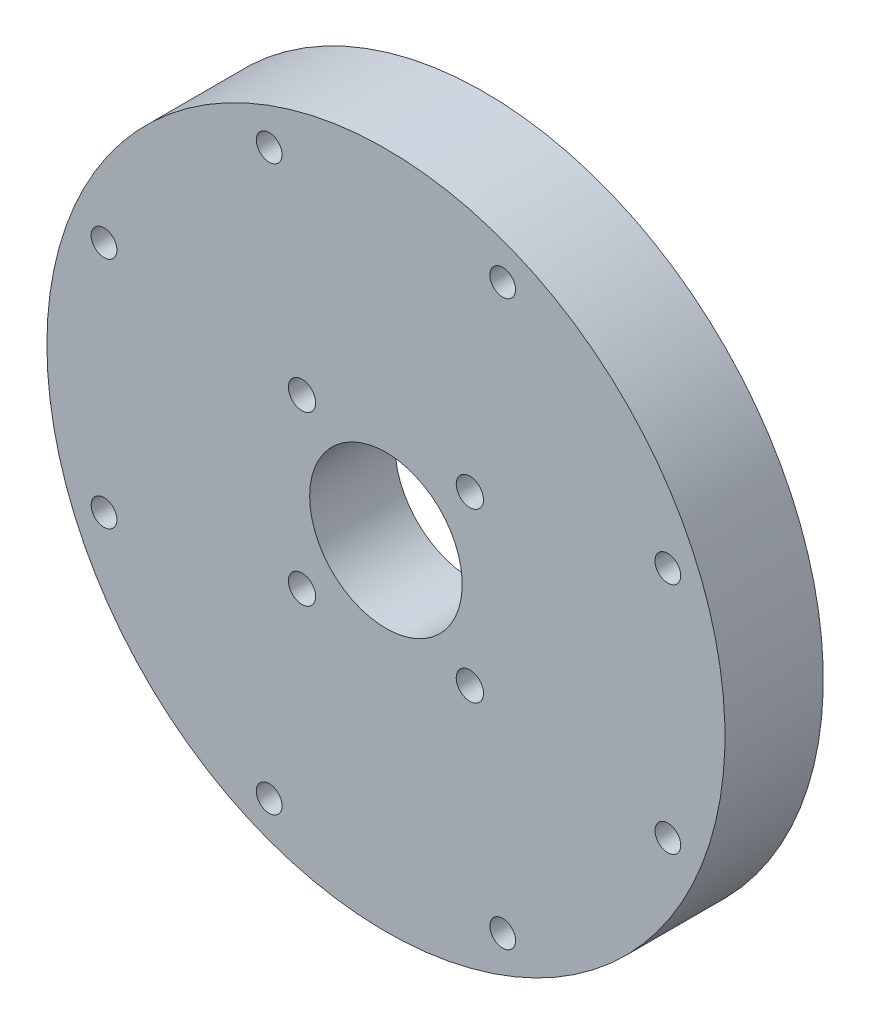
SolidWorks part; units mm, degrees
material "6061-T6 (SS)"
ref_plane "Front Plane" through (0, 0, 0) normal (0, 0, 1) x (1, 0, 0)
ref_plane "Top Plane" through (0, 0, 0) normal (0, 1, 0) x (1, 0, 0)
ref_plane "Right Plane" through (0, 0, 0) normal (1, 0, 0) x (0, 0, -1)
curve "Volute Curve"
  spline degree 3 poles (34.2618, 0, 0) (34.2648, 0.0718, 0) (34.2707, 0.2156, 0) (34.2778, 0.4312, 0) (34.2837, 0.647, 0) (34.2882, 0.8628, 0) (34.2914, 1.0787, 0) (34.2932, 1.2947, 0) (34.2937, 1.5108, 0) (34.2929, 1.7269, 0) (34.2907, 1.9431, 0) (34.2871, 2.1593, 0) (34.2822, 2.3756, 0) (34.2759, 2.5919, 0) (34.2683, 2.8082, 0) (34.2593, 3.0245, 0) (34.2489, 3.2407, 0) (34.2372, 3.457, 0) (34.2242, 3.6733, 0) (34.2098, 3.8895, 0) (34.194, 4.1058, 0) (34.1768, 4.3219, 0) (34.1583, 4.538, 0) (34.1385, 4.7541, 0) (34.1173, 4.9701, 0) (34.0947, 5.186, 0) (34.0708, 5.4018, 0) (34.0454, 5.6175, 0) (34.0188, 5.8331, 0) (33.9908, 6.0486, 0) (33.9614, 6.264, 0) (33.9306, 6.4793, 0) (33.8985, 6.6944, 0) (33.8651, 6.9094, 0) (33.8303, 7.1242, 0) (33.7941, 7.3388, 0) (33.7566, 7.5533, 0) (33.7177, 7.7676, 0) (33.6774, 7.9817, 0) (33.6358, 8.1956, 0) (33.5929, 8.4093, 0) (33.5486, 8.6228, 0) (33.5029, 8.8361, 0) (33.4559, 9.0491, 0) (33.4076, 9.2619, 0) (33.3579, 9.4745, 0) (33.3068, 9.6868, 0) (33.2544, 9.8988, 0) (33.2006, 10.1105, 0) (33.1456, 10.322, 0) (33.0891, 10.5332, 0) (33.0313, 10.744, 0) (32.9722, 10.9546, 0) (32.9118, 11.1648, 0) (32.85, 11.3748, 0) (32.7869, 11.5843, 0) (32.7224, 11.7936, 0) (32.6566, 12.0025, 0) (32.5895, 12.211, 0) (32.521, 12.4192, 0) (32.4513, 12.627, 0) (32.3802, 12.8344, 0) (32.3077, 13.0414, 0) (32.234, 13.248, 0) (32.1589, 13.4542, 0) (32.0826, 13.6599, 0) (32.0049, 13.8653, 0) (31.9259, 14.0702, 0) (31.8456, 14.2747, 0) (31.764, 14.4787, 0) (31.6811, 14.6823, 0) (31.5968, 14.8854, 0) (31.5113, 15.088, 0) (31.4245, 15.2901, 0) (31.3364, 15.4917, 0) (31.247, 15.6929, 0) (31.1563, 15.8935, 0) (31.0644, 16.0936, 0) (30.9711, 16.2932, 0) (30.8766, 16.4922, 0) (30.7808, 16.6907, 0) (30.6837, 16.8886, 0) (30.5854, 17.086, 0) (30.4858, 17.2829, 0) (30.3849, 17.4791, 0) (30.2828, 17.6748, 0) (30.1794, 17.8698, 0) (30.0747, 18.0643, 0) (29.9688, 18.2582, 0) (29.8617, 18.4514, 0) (29.7533, 18.644, 0) (29.6437, 18.836, 0) (29.5328, 19.0274, 0) (29.4208, 19.2181, 0) (29.3074, 19.4081, 0) (29.1929, 19.5975, 0) (29.0771, 19.7862, 0) (28.9601, 19.9742, 0) (28.842, 20.1616, 0) (28.7226, 20.3482, 0) (28.602, 20.5342, 0) (28.4801, 20.7194, 0) (28.3571, 20.904, 0) (28.233, 21.0877, 0) (28.1076, 21.2708, 0) (27.981, 21.4531, 0) (27.8533, 21.6347, 0) (27.7243, 21.8155, 0) (27.5942, 21.9956, 0) (27.463, 22.1748, 0) (27.3306, 22.3533, 0) (27.197, 22.531, 0) (27.0623, 22.708, 0) (26.9264, 22.8841, 0) (26.7894, 23.0594, 0) (26.6512, 23.2339, 0) (26.5119, 23.4075, 0) (26.3715, 23.5804, 0) (26.23, 23.7524, 0) (26.0873, 23.9235, 0) (25.9435, 24.0938, 0) (25.7987, 24.2632, 0) (25.6527, 24.4318, 0) (25.5056, 24.5995, 0) (25.3574, 24.7663, 0) (25.2082, 24.9322, 0) (25.0578, 25.0973, 0) (24.9064, 25.2614, 0) (24.7539, 25.4246, 0) (24.6003, 25.5869, 0) (24.4457, 25.7483, 0) (24.29, 25.9087, 0) (24.1333, 26.0682, 0) (23.9755, 26.2268, 0) (23.8167, 26.3844, 0) (23.6569, 26.541, 0) (23.496, 26.6967, 0) (23.3341, 26.8514, 0) (23.1712, 27.0051, 0) (23.0073, 27.1579, 0) (22.8424, 27.3096, 0) (22.6765, 27.4604, 0) (22.5096, 27.6101, 0) (22.3417, 27.7589, 0) (22.1728, 27.9066, 0) (22.003, 28.0533, 0) (21.8322, 28.199, 0) (21.6604, 28.3436, 0) (21.4877, 28.4872, 0) (21.314, 28.6297, 0) (21.1394, 28.7712, 0) (20.9639, 28.9116, 0) (20.7874, 29.051, 0) (20.61, 29.1892, 0) (20.4317, 29.3264, 0) (20.2524, 29.4626, 0) (20.0723, 29.5976, 0) (19.8913, 29.7315, 0) (19.7094, 29.8643, 0) (19.5266, 29.996, 0) (19.3429, 30.1266, 0) (19.1584, 30.2561, 0) (18.973, 30.3844, 0) (18.7867, 30.5116, 0) (18.5996, 30.6377, 0) (18.4117, 30.7626, 0) (18.2229, 30.8864, 0) (18.0333, 31.009, 0) (17.8429, 31.1304, 0) (17.6516, 31.2507, 0) (17.4596, 31.3698, 0) (17.2667, 31.4878, 0) (17.0731, 31.6045, 0) (16.8786, 31.7201, 0) (16.6834, 31.8344, 0) (16.4875, 31.9476, 0) (16.2907, 32.0596, 0) (16.0932, 32.1703, 0) (15.895, 32.2799, 0) (15.696, 32.3882, 0) (15.4963, 32.4953, 0) (15.2959, 32.6012, 0) (15.0947, 32.7058, 0) (14.8929, 32.8092, 0) (14.6903, 32.9114, 0) (14.487, 33.0123, 0) (14.2831, 33.1119, 0) (14.0784, 33.2103, 0) (13.8731, 33.3075, 0) (13.6672, 33.4033, 0) (13.4606, 33.4979, 0) (13.2533, 33.5912, 0) (13.0454, 33.6833, 0) (12.8368, 33.774, 0) (12.6277, 33.8635, 0) (12.4179, 33.9517, 0) (12.2075, 34.0385, 0) (11.9965, 34.1241, 0) (11.7849, 34.2084, 0) (11.5727, 34.2913, 0) (11.36, 34.373, 0) (11.1467, 34.4533, 0) (10.9328, 34.5323, 0) (10.7183, 34.61, 0) (10.5034, 34.6863, 0) (10.2879, 34.7613, 0) (10.0718, 34.835, 0) (9.8553, 34.9074, 0) (9.6382, 34.9783, 0) (9.4206, 35.048, 0) (9.2025, 35.1163, 0) (8.984, 35.1832, 0) (8.765, 35.2488, 0) (8.5455, 35.313, 0) (8.3255, 35.3759, 0) (8.1051, 35.4374, 0) (7.8842, 35.4975, 0) (7.6629, 35.5562, 0) (7.4412, 35.6136, 0) (7.2191, 35.6696, 0) (6.9965, 35.7242, 0) (6.7736, 35.7774, 0) (6.5503, 35.8292, 0) (6.3265, 35.8796, 0) (6.1024, 35.9287, 0) (5.878, 35.9763, 0) (5.6532, 36.0225, 0) (5.428, 36.0674, 0) (5.2025, 36.1108, 0) (4.9766, 36.1528, 0) (4.7505, 36.1934, 0) (4.524, 36.2326, 0) (4.2972, 36.2704, 0) (4.0701, 36.3067, 0) (3.8428, 36.3417, 0) (3.6151, 36.3752, 0) (3.3872, 36.4073, 0) (3.159, 36.438, 0) (2.9306, 36.4672, 0) (2.7019, 36.495, 0) (2.473, 36.5214, 0) (2.2439, 36.5463, 0) (2.0146, 36.5699, 0) (1.785, 36.5919, 0) (1.5553, 36.6126, 0) (1.3253, 36.6318, 0) (1.0952, 36.6495, 0) (0.8649, 36.6658, 0) (0.6345, 36.6807, 0) (0.4039, 36.6941, 0) (0.1731, 36.706, 0) (-0.0577, 36.7166, 0) (-0.2887, 36.7256, 0) (-0.5199, 36.7332, 0) (-0.7511, 36.7394, 0) (-0.9824, 36.7441, 0) (-1.2138, 36.7474, 0) (-1.4453, 36.7492, 0) (-1.6769, 36.7495, 0) (-1.9085, 36.7484, 0) (-2.1402, 36.7458, 0) (-2.3719, 36.7418, 0) (-2.6037, 36.7363, 0) (-2.8355, 36.7293, 0) (-3.0673, 36.7209, 0) (-3.2991, 36.711, 0) (-3.5309, 36.6997, 0) (-3.7627, 36.6869, 0) (-3.9944, 36.6726, 0) (-4.2262, 36.6569, 0) (-4.4579, 36.6397, 0) (-4.6895, 36.6211, 0) (-4.9211, 36.6009, 0) (-5.1526, 36.5794, 0) (-5.3841, 36.5563, 0) (-5.6154, 36.5318, 0) (-5.8467, 36.5059, 0) (-6.0779, 36.4784, 0) (-6.3089, 36.4495, 0) (-6.5399, 36.4192, 0) (-6.7706, 36.3874, 0) (-7.0013, 36.3541, 0) (-7.2318, 36.3194, 0) (-7.4621, 36.2832, 0) (-7.6923, 36.2455, 0) (-7.9223, 36.2064, 0) (-8.1521, 36.1658, 0) (-8.3817, 36.1238, 0) (-8.6111, 36.0803, 0) (-8.8403, 36.0354, 0) (-9.0693, 35.989, 0) (-9.298, 35.9411, 0) (-9.5265, 35.8918, 0) (-9.7548, 35.8411, 0) (-9.9827, 35.7889, 0) (-10.2105, 35.7352, 0) (-10.4379, 35.6802, 0) (-10.665, 35.6236, 0) (-10.8919, 35.5656, 0) (-11.1184, 35.5062, 0) (-11.3446, 35.4453, 0) (-11.5705, 35.383, 0) (-11.7961, 35.3193, 0) (-12.0213, 35.2541, 0) (-12.2461, 35.1875, 0) (-12.4706, 35.1194, 0) (-12.6948, 35.0499, 0) (-12.9185, 34.979, 0) (-13.1419, 34.9067, 0) (-13.3648, 34.8329, 0) (-13.5874, 34.7578, 0) (-13.8095, 34.6812, 0) (-14.0312, 34.6031, 0) (-14.2525, 34.5237, 0) (-14.4734, 34.4429, 0) (-14.6937, 34.3606, 0) (-14.9137, 34.2769, 0) (-15.1331, 34.1918, 0) (-15.3521, 34.1054, 0) (-15.5706, 34.0175, 0) (-15.7885, 33.9282, 0) (-16.006, 33.8375, 0) (-16.223, 33.7455, 0) (-16.4394, 33.652, 0) (-16.6553, 33.5572, 0) (-16.8707, 33.461, 0) (-17.0855, 33.3634, 0) (-17.2997, 33.2644, 0) (-17.5134, 33.164, 0) (-17.7265, 33.0623, 0) (-17.939, 32.9592, 0) (-18.151, 32.8548, 0) (-18.3623, 32.7489, 0) (-18.573, 32.6418, 0) (-18.7831, 32.5332, 0) (-18.9925, 32.4234, 0) (-19.2014, 32.3121, 0) (-19.4095, 32.1996, 0) (-19.6171, 32.0857, 0) (-19.8239, 31.9704, 0) (-20.0301, 31.8538, 0) (-20.2356, 31.7359, 0) (-20.4404, 31.6167, 0) (-20.6445, 31.4962, 0) (-20.8479, 31.3743, 0) (-21.0506, 31.2511, 0) (-21.2526, 31.1267, 0) (-21.4538, 31.0009, 0) (-21.6543, 30.8738, 0) (-21.854, 30.7454, 0) (-22.053, 30.6158, 0) (-22.2512, 30.4848, 0) (-22.4487, 30.3526, 0) (-22.6453, 30.2191, 0) (-22.8412, 30.0843, 0) (-23.0363, 29.9482, 0) (-23.2305, 29.8109, 0) (-23.424, 29.6723, 0) (-23.6166, 29.5325, 0) (-23.8084, 29.3915, 0) (-23.9994, 29.2491, 0) (-24.1895, 29.1056, 0) (-24.3787, 28.9608, 0) (-24.5671, 28.8148, 0) (-24.7546, 28.6676, 0) (-24.9413, 28.5191, 0) (-25.127, 28.3694, 0) (-25.3119, 28.2186, 0) (-25.4958, 28.0665, 0) (-25.6789, 27.9132, 0) (-25.861, 27.7587, 0) (-26.0422, 27.6031, 0) (-26.2224, 27.4463, 0) (-26.4018, 27.2882, 0) (-26.5801, 27.1291, 0) (-26.7576, 26.9687, 0) (-26.934, 26.8072, 0) (-27.1095, 26.6446, 0) (-27.284, 26.4808, 0) (-27.4575, 26.3159, 0) (-27.63, 26.1498, 0) (-27.8015, 25.9826, 0) (-27.972, 25.8143, 0) (-28.1415, 25.6448, 0) (-28.31, 25.4743, 0) (-28.4774, 25.3027, 0) (-28.6438, 25.1299, 0) (-28.8092, 24.9561, 0) (-28.9735, 24.7811, 0) (-29.1367, 24.6051, 0) (-29.2989, 24.4281, 0) (-29.46, 24.2499, 0) (-29.62, 24.0707, 0) (-29.7789, 23.8905, 0) (-29.9368, 23.7092, 0) (-30.0935, 23.5268, 0) (-30.2491, 23.3435, 0) (-30.4036, 23.1591, 0) (-30.557, 22.9737, 0) (-30.7093, 22.7872, 0) (-30.8604, 22.5998, 0) (-31.0104, 22.4114, 0) (-31.1592, 22.2219, 0) (-31.3069, 22.0315, 0) (-31.4534, 21.8402, 0) (-31.5988, 21.6478, 0) (-31.7429, 21.4545, 0) (-31.8859, 21.2602, 0) (-32.0277, 21.065, 0) (-32.1684, 20.8688, 0) (-32.3078, 20.6717, 0) (-32.446, 20.4737, 0) (-32.583, 20.2747, 0) (-32.7188, 20.0748, 0) (-32.8533, 19.8741, 0) (-32.9866, 19.6724, 0) (-33.1187, 19.4698, 0) (-33.2496, 19.2664, 0) (-33.3792, 19.0621, 0) (-33.5075, 18.8569, 0) (-33.6346, 18.6509, 0) (-33.7604, 18.444, 0) (-33.885, 18.2362, 0) (-34.0082, 18.0276, 0) (-34.1302, 17.8182, 0) (-34.2509, 17.608, 0) (-34.3703, 17.397, 0) (-34.4884, 17.1851, 0) (-34.6052, 16.9725, 0) (-34.7207, 16.7591, 0) (-34.8349, 16.5449, 0) (-34.9478, 16.3299, 0) (-35.0593, 16.1141, 0) (-35.1695, 15.8976, 0) (-35.2784, 15.6804, 0) (-35.3859, 15.4624, 0) (-35.4921, 15.2436, 0) (-35.597, 15.0242, 0) (-35.7004, 14.804, 0) (-35.8026, 14.5832, 0) (-35.9033, 14.3616, 0) (-36.0027, 14.1393, 0) (-36.1007, 13.9164, 0) (-36.1973, 13.6928, 0) (-36.2926, 13.4685, 0) (-36.3864, 13.2436, 0) (-36.4789, 13.018, 0) (-36.57, 12.7918, 0) (-36.6596, 12.5649, 0) (-36.7479, 12.3374, 0) (-36.8348, 12.1094, 0) (-36.9202, 11.8807, 0) (-37.0042, 11.6514, 0) (-37.0868, 11.4215, 0) (-37.168, 11.1911, 0) (-37.2477, 10.96, 0) (-37.326, 10.7285, 0) (-37.4029, 10.4963, 0) (-37.4783, 10.2637, 0) (-37.5523, 10.0305, 0) (-37.6248, 9.7967, 0) (-37.6959, 9.5625, 0) (-37.7655, 9.3277, 0) (-37.8337, 9.0925, 0) (-37.9004, 8.8568, 0) (-37.9656, 8.6205, 0) (-38.0293, 8.3839, 0) (-38.0916, 8.1467, 0) (-38.1524, 7.9091, 0) (-38.2117, 7.6711, 0) (-38.2696, 7.4326, 0) (-38.3259, 7.1937, 0) (-38.3808, 6.9544, 0) (-38.4342, 6.7147, 0) (-38.486, 6.4746, 0) (-38.5364, 6.2341, 0) (-38.5853, 5.9932, 0) (-38.6326, 5.7519, 0) (-38.6785, 5.5103, 0) (-38.7229, 5.2684, 0) (-38.7657, 5.0261, 0) (-38.807, 4.7835, 0) (-38.8468, 4.5405, 0) (-38.8851, 4.2973, 0) (-38.9219, 4.0537, 0) (-38.9571, 3.8099, 0) (-38.9908, 3.5657, 0) (-39.023, 3.3213, 0) (-39.0537, 3.0767, 0) (-39.0828, 2.8317, 0) (-39.1104, 2.5866, 0) (-39.1364, 2.3412, 0) (-39.1609, 2.0955, 0) (-39.1839, 1.8497, 0) (-39.2053, 1.6037, 0) (-39.2252, 1.3574, 0) (-39.2435, 1.111, 0) (-39.2603, 0.8644, 0) (-39.2756, 0.6176, 0) (-39.2893, 0.3707, 0) (-39.3014, 0.1236, 0) (-39.312, -0.1236, 0) (-39.321, -0.371, 0) (-39.3285, -0.6185, 0) (-39.3344, -0.866, 0) (-39.3388, -1.1137, 0) (-39.3416, -1.3615, 0) (-39.3428, -1.6093, 0) (-39.3425, -1.8572, 0) (-39.3406, -2.1052, 0) (-39.3372, -2.3532, 0) (-39.3322, -2.6013, 0) (-39.3257, -2.8494, 0) (-39.3175, -3.0975, 0) (-39.3078, -3.3456, 0) (-39.2966, -3.5937, 0) (-39.2838, -3.8418, 0) (-39.2694, -4.0899, 0) (-39.2534, -4.338, 0) (-39.2359, -4.586, 0) (-39.2168, -4.834, 0) (-39.1962, -5.0819, 0) (-39.174, -5.3298, 0) (-39.1502, -5.5776, 0) (-39.1248, -5.8252, 0) (-39.0979, -6.0728, 0) (-39.0694, -6.3203, 0) (-39.0394, -6.5677, 0) (-39.0078, -6.8149, 0) (-38.9746, -7.062, 0) (-38.9399, -7.309, 0) (-38.9036, -7.5558, 0) (-38.8657, -7.8024, 0) (-38.8263, -8.0488, 0) (-38.7853, -8.2951, 0) (-38.7427, -8.5411, 0) (-38.6986, -8.787, 0) (-38.653, -9.0326, 0) (-38.6057, -9.2781, 0) (-38.557, -9.5232, 0) (-38.5066, -9.7682, 0) (-38.4547, -10.0128, 0) (-38.4013, -10.2572, 0) (-38.3463, -10.5014, 0) (-38.2897, -10.7452, 0) (-38.2316, -10.9888, 0) (-38.172, -11.232, 0) (-38.1108, -11.475, 0) (-38.048, -11.7176, 0) (-37.9838, -11.9598, 0) (-37.9179, -12.2018, 0) (-37.8506, -12.4433, 0) (-37.7817, -12.6845, 0) (-37.7112, -12.9254, 0) (-37.6393, -13.1658, 0) (-37.5658, -13.4059, 0) (-37.4907, -13.6455, 0) (-37.4142, -13.8848, 0) (-37.3361, -14.1236, 0) (-37.2565, -14.362, 0) (-37.1753, -14.5999, 0) (-37.0927, -14.8374, 0) (-37.0085, -15.0744, 0) (-36.9228, -15.311, 0) (-36.8357, -15.547, 0) (-36.747, -15.7826, 0) (-36.6568, -16.0177, 0) (-36.5651, -16.2523, 0) (-36.4719, -16.4863, 0) (-36.3772, -16.7199, 0) (-36.281, -16.9528, 0) (-36.1833, -17.1853, 0) (-36.0841, -17.4172, 0) (-35.9834, -17.6485, 0) (-35.8813, -17.8792, 0) (-35.7777, -18.1094, 0) (-35.6726, -18.3389, 0) (-35.566, -18.5679, 0) (-35.458, -18.7962, 0) (-35.3485, -19.0239, 0) (-35.2376, -19.251, 0) (-35.1251, -19.4774, 0) (-35.0113, -19.7032, 0) (-34.896, -19.9283, 0) (-34.7792, -20.1528, 0) (-34.661, -20.3765, 0) (-34.5414, -20.5996, 0) (-34.4203, -20.822, 0) (-34.2978, -21.0437, 0) (-34.1738, -21.2646, 0) (-34.0485, -21.4849, 0) (-33.9217, -21.7044, 0) (-33.7935, -21.9231, 0) (-33.6639, -22.1411, 0) (-33.5329, -22.3584, 0) (-33.4005, -22.5748, 0) (-33.2667, -22.7905, 0) (-33.1315, -23.0054, 0) (-32.995, -23.2195, 0) (-32.857, -23.4328, 0) (-32.7177, -23.6453, 0) (-32.577, -23.8569, 0) (-32.4349, -24.0677, 0) (-32.2915, -24.2777, 0) (-32.1467, -24.4868, 0) (-32.0006, -24.6951, 0) (-31.8531, -24.9025, 0) (-31.7042, -25.109, 0) (-31.5541, -25.3146, 0) (-31.4026, -25.5194, 0) (-31.2497, -25.7232, 0) (-31.0956, -25.9261, 0) (-30.9401, -26.1281, 0) (-30.7833, -26.3292, 0) (-30.6253, -26.5293, 0) (-30.4659, -26.7285, 0) (-30.3052, -26.9267, 0) (-30.1433, -27.124, 0) (-29.98, -27.3203, 0) (-29.8155, -27.5156, 0) (-29.6497, -27.7099, 0) (-29.4827, -27.9032, 0) (-29.3144, -28.0956, 0) (-29.1448, -28.2869, 0) (-28.974, -28.4772, 0) (-28.8019, -28.6664, 0) (-28.6287, -28.8546, 0) (-28.4542, -29.0418, 0) (-28.2784, -29.2279, 0) (-28.1015, -29.413, 0) (-27.9233, -29.597, 0) (-27.744, -29.7799, 0) (-27.5634, -29.9618, 0) (-27.3817, -30.1425, 0) (-27.1987, -30.3221, 0) (-27.0146, -30.5007, 0) (-26.8294, -30.6781, 0) (-26.6429, -30.8544, 0) (-26.4554, -31.0296, 0) (-26.2666, -31.2036, 0) (-26.0767, -31.3765, 0) (-25.8857, -31.5482, 0) (-25.6936, -31.7188, 0) (-25.5003, -31.8882, 0) (-25.306, -32.0564, 0) (-25.1105, -32.2234, 0) (-24.9139, -32.3893, 0) (-24.7162, -32.5539, 0) (-24.5175, -32.7174, 0) (-24.3176, -32.8796, 0) (-24.1167, -33.0406, 0) (-23.9147, -33.2004, 0) (-23.7117, -33.359, 0) (-23.5076, -33.5163, 0) (-23.3025, -33.6724, 0) (-23.0964, -33.8272, 0) (-22.8892, -33.9807, 0) (-22.681, -34.133, 0) (-22.4718, -34.2841, 0) (-22.2616, -34.4338, 0) (-22.0504, -34.5822, 0) (-21.8382, -34.7294, 0) (-21.6251, -34.8752, 0) (-21.4109, -35.0198, 0) (-21.1959, -35.163, 0) (-20.9798, -35.3049, 0) (-20.7628, -35.4455, 0) (-20.5449, -35.5848, 0) (-20.326, -35.7227, 0) (-20.1062, -35.8593, 0) (-19.8855, -35.9945, 0) (-19.6639, -36.1284, 0) (-19.4414, -36.2609, 0) (-19.2181, -36.392, 0) (-18.9938, -36.5218, 0) (-18.7686, -36.6502, 0) (-18.5426, -36.7772, 0) (-18.3158, -36.9028, 0) (-18.0881, -37.027, 0) (-17.8595, -37.1498, 0) (-17.6302, -37.2712, 0) (-17.4, -37.3911, 0) (-17.169, -37.5097, 0) (-16.9372, -37.6268, 0) (-16.7046, -37.7425, 0) (-16.4712, -37.8568, 0) (-16.237, -37.9696, 0) (-16.0021, -38.081, 0) (-15.7664, -38.1909, 0) (-15.53, -38.2994, 0) (-15.2928, -38.4064, 0) (-15.0549, -38.5119, 0) (-14.8163, -38.616, 0) (-14.577, -38.7185, 0) (-14.3369, -38.8196, 0) (-14.0962, -38.9192, 0) (-13.8547, -39.0174, 0) (-13.6126, -39.114, 0) (-13.3699, -39.2091, 0) (-13.1265, -39.3027, 0) (-12.8824, -39.3949, 0) (-12.6377, -39.4854, 0) (-12.3923, -39.5745, 0) (-12.1464, -39.6621, 0) (-11.8998, -39.7481, 0) (-11.6526, -39.8326, 0) (-11.4048, -39.9155, 0) (-11.1565, -39.997, 0) (-10.9076, -40.0768, 0) (-10.6581, -40.1552, 0) (-10.408, -40.2319, 0) (-10.1575, -40.3071, 0) (-9.9063, -40.3808, 0) (-9.6547, -40.4529, 0) (-9.4025, -40.5234, 0) (-9.1499, -40.5924, 0) (-8.8967, -40.6598, 0) (-8.6431, -40.7256, 0) (-8.389, -40.7898, 0) (-8.1344, -40.8524, 0) (-7.8793, -40.9135, 0) (-7.6239, -40.9729, 0) (-7.3679, -41.0308, 0) (-7.1116, -41.087, 0) (-6.8548, -41.1417, 0) (-6.5977, -41.1948, 0) (-6.3401, -41.2462, 0) (-6.0821, -41.2961, 0) (-5.8238, -41.3443, 0) (-5.5651, -41.3909, 0) (-5.3061, -41.4359, 0) (-5.0467, -41.4793, 0) (-4.7869, -41.5211, 0) (-4.5269, -41.5612, 0) (-4.2665, -41.5997, 0) (-4.0058, -41.6366, 0) (-3.7449, -41.6718, 0) (-3.4836, -41.7054, 0) (-3.2221, -41.7374, 0) (-2.9603, -41.7677, 0) (-2.6982, -41.7964, 0) (-2.4359, -41.8234, 0) (-2.1734, -41.8488, 0) (-1.9106, -41.8726, 0) (-1.6477, -41.8947, 0) (-1.3845, -41.9151, 0) (-1.1212, -41.9339, 0) (-0.8576, -41.9511, 0) (-0.5939, -41.9666, 0) (-0.33, -41.9804, 0) (-0.066, -41.9926, 0) (0.1981, -42.0031, 0) (0.4624, -42.012, 0) (0.7268, -42.0192, 0) (0.9914, -42.0247, 0) (1.256, -42.0286, 0) (1.5207, -42.0308, 0) (1.7855, -42.0313, 0) (2.0503, -42.0302, 0) (2.3152, -42.0274, 0) (2.5802, -42.0229, 0) (2.8452, -42.0168, 0) (3.1102, -42.0089, 0) (3.3752, -41.9995, 0) (3.6403, -41.9883, 0) (3.9053, -41.9755, 0) (4.1703, -41.961, 0) (4.4353, -41.9448, 0) (4.7002, -41.927, 0) (4.9651, -41.9075, 0) (5.2299, -41.8863, 0) (5.4947, -41.8634, 0) (5.7594, -41.8389, 0) (6.024, -41.8127, 0) (6.2885, -41.7848, 0) (6.5528, -41.7553, 0) (6.8171, -41.7241, 0) (7.0812, -41.6912, 0) (7.3452, -41.6566, 0) (7.609, -41.6204, 0) (7.8727, -41.5825, 0) (8.1362, -41.5429, 0) (8.3995, -41.5017, 0) (8.6626, -41.4588, 0) (8.9254, -41.4142, 0) (9.1881, -41.3679, 0) (9.4506, -41.32, 0) (9.7128, -41.2705, 0) (9.9747, -41.2192, 0) (10.2364, -41.1663, 0) (10.4979, -41.1118, 0) (10.759, -41.0556, 0) (11.0199, -40.9977, 0) (11.2804, -40.9382, 0) (11.5407, -40.877, 0) (11.8006, -40.8141, 0) (12.0602, -40.7496, 0) (12.3194, -40.6835, 0) (12.5783, -40.6157, 0) (12.8368, -40.5463, 0) (13.0949, -40.4752, 0) (13.3527, -40.4025, 0) (13.6101, -40.3281, 0) (13.867, -40.2521, 0) (14.1235, -40.1745, 0) (14.3797, -40.0952, 0) (14.6353, -40.0143, 0) (14.8905, -39.9318, 0) (15.1453, -39.8476, 0) (15.3996, -39.7618, 0) (15.6534, -39.6744, 0) (15.9067, -39.5854, 0) (16.1596, -39.4948, 0) (16.4119, -39.4025, 0) (16.6637, -39.3087, 0) (16.9149, -39.2132, 0) (17.1657, -39.1161, 0) (17.4158, -39.0174, 0) (17.6654, -38.9172, 0) (17.9145, -38.8153, 0) (18.1629, -38.7118, 0) (18.4108, -38.6068, 0) (18.658, -38.5001, 0) (18.9047, -38.3919, 0) (19.1507, -38.2821, 0) (19.3961, -38.1707, 0) (19.6408, -38.0578, 0) (19.8849, -37.9433, 0) (20.1283, -37.8272, 0) (20.3711, -37.7095, 0) (20.6132, -37.5904, 0) (20.8546, -37.4696, 0) (21.0952, -37.3473, 0) (21.3352, -37.2235, 0) (21.5744, -37.0981, 0) (21.8129, -36.9712, 0) (22.0507, -36.8427, 0) (22.2877, -36.7127, 0) (22.524, -36.5812, 0) (22.7594, -36.4482, 0) (22.9941, -36.3137, 0) (23.228, -36.1776, 0) (23.4611, -36.0401, 0) (23.6934, -35.901, 0) (23.9249, -35.7605, 0) (24.1556, -35.6184, 0) (24.3854, -35.4749, 0) (24.6143, -35.3299, 0) (24.8424, -35.1834, 0) (25.0696, -35.0355, 0) (25.296, -34.8861, 0) (25.5214, -34.7352, 0) (25.746, -34.5828, 0) (25.9696, -34.4291, 0) (26.1924, -34.2738, 0) (26.4142, -34.1172, 0) (26.6351, -33.9591, 0) (26.855, -33.7995, 0) (27.074, -33.6386, 0) (27.292, -33.4762, 0) (27.5091, -33.3124, 0) (27.7252, -33.1472, 0) (27.9402, -32.9807, 0) (28.1543, -32.8127, 0) (28.3674, -32.6433, 0) (28.5795, -32.4726, 0) (28.7905, -32.3004, 0) (29.0005, -32.127, 0) (29.2095, -31.9521, 0) (29.4174, -31.7759, 0) (29.6242, -31.5983, 0) (29.83, -31.4194, 0) (30.0347, -31.2392, 0) (30.2383, -31.0576, 0) (30.4408, -30.8747, 0) (30.6422, -30.6905, 0) (30.8426, -30.5049, 0) (31.0417, -30.3181, 0) (31.2398, -30.1299, 0) (31.4367, -29.9405, 0) (31.6325, -29.7498, 0) (31.8271, -29.5578, 0) (32.0205, -29.3645, 0) (32.2128, -29.17, 0) (32.4039, -28.9742, 0) (32.5938, -28.7772, 0) (32.7825, -28.5789, 0) (32.97, -28.3794, 0) (33.1563, -28.1787, 0) (33.3414, -27.9767, 0) (33.5252, -27.7736, 0) (33.7079, -27.5692, 0) (33.8892, -27.3636, 0) (34.0693, -27.1569, 0) (34.2482, -26.9489, 0) (34.4258, -26.7398, 0) (34.6021, -26.5295, 0) (34.7771, -26.3181, 0) (34.9509, -26.1055, 0) (35.1233, -25.8917, 0) (35.2944, -25.6768, 0) (35.4643, -25.4608, 0) (35.6328, -25.2437, 0) (35.7999, -25.0255, 0) (35.9658, -24.8061, 0) (36.1303, -24.5857, 0) (36.2934, -24.3641, 0) (36.4552, -24.1415, 0) (36.6157, -23.9179, 0) (36.7747, -23.6931, 0) (36.9324, -23.4673, 0) (37.0887, -23.2405, 0) (37.2436, -23.0126, 0) (37.3971, -22.7837, 0) (37.5492, -22.5538, 0) (37.6999, -22.3228, 0) (37.8491, -22.0909, 0) (37.997, -21.858, 0) (38.1434, -21.624, 0) (38.2884, -21.3891, 0) (38.4319, -21.1533, 0) (38.574, -20.9165, 0) (38.7146, -20.6787, 0) (38.8537, -20.44, 0) (38.9914, -20.2003, 0) (39.1276, -19.9598, 0) (39.2623, -19.7183, 0) (39.3956, -19.4759, 0) (39.5273, -19.2326, 0) (39.6575, -18.9884, 0) (39.7863, -18.7434, 0) (39.9135, -18.4975, 0) (40.0392, -18.2507, 0) (40.1633, -18.0031, 0) (40.286, -17.7546, 0) (40.4071, -17.5053, 0) (40.5267, -17.2552, 0) (40.6447, -17.0043, 0) (40.7611, -16.7525, 0) (40.876, -16.5, 0) (40.9894, -16.2467, 0) (41.1012, -15.9927, 0) (41.2114, -15.7378, 0) (41.32, -15.4822, 0) (41.427, -15.2259, 0) (41.5325, -14.9688, 0) (41.6363, -14.711, 0) (41.7386, -14.4525, 0) (41.8392, -14.1933, 0) (41.9383, -13.9334, 0) (42.0357, -13.6728, 0) (42.1315, -13.4116, 0) (42.2257, -13.1496, 0) (42.3182, -12.8871, 0) (42.4092, -12.6238, 0) (42.4985, -12.36, 0) (42.5861, -12.0955, 0) (42.6721, -11.8304, 0) (42.7565, -11.5647, 0) (42.8392, -11.2984, 0) (42.9202, -11.0315, 0) (42.9996, -10.7641, 0) (43.0773, -10.4961, 0) (43.1534, -10.2275, 0) (43.2277, -9.9584, 0) (43.3004, -9.6888, 0) (43.3715, -9.4186, 0) (43.4408, -9.148, 0) (43.5084, -8.8768, 0) (43.5744, -8.6052, 0) (43.6386, -8.333, 0) (43.7012, -8.0604, 0) (43.7621, -7.7874, 0) (43.8212, -7.5139, 0) (43.8786, -7.24, 0) (43.9344, -6.9656, 0) (43.9884, -6.6908, 0) (44.0407, -6.4156, 0) (44.0913, -6.1401, 0) (44.1401, -5.8641, 0) (44.1872, -5.5878, 0) (44.2326, -5.3111, 0) (44.2763, -5.0341, 0) (44.3182, -4.7567, 0) (44.3584, -4.479, 0) (44.3969, -4.201, 0) (44.4336, -3.9226, 0) (44.4686, -3.644, 0) (44.5018, -3.3651, 0) (44.5333, -3.0859, 0) (44.563, -2.8065, 0) (44.591, -2.5268, 0) (44.6172, -2.2468, 0) (44.6416, -1.9667, 0) (44.6643, -1.6863, 0) (44.6853, -1.4057, 0) (44.7044, -1.1249, 0) (44.7219, -0.8439, 0) (44.7375, -0.5628, 0) (44.7515, -0.2815, 0) (44.7593, -0.0938, 0) (44.7632, 0, 0) knots 0 0 0 0 0.000871 0.001743 0.002614 0.003486 0.004358 0.005231 0.006103 0.006976 0.007849 0.008723 0.009596 0.01047 0.011344 0.012219 0.013093 0.013968 0.014843 0.015718 0.016594 0.017469 0.018345 0.019222 0.020098 0.020975 0.021852 0.022729 0.023606 0.024484 0.025362 0.02624 0.027119 0.027997 0.028876 0.029755 0.030635 0.031514 0.032394 0.033274 0.034154 0.035035 0.035916 0.036797 0.037678 0.03856 0.039442 0.040324 0.041206 0.042089 0.042971 0.043854 0.044738 0.045621 0.046505 0.047389 0.048273 0.049158 0.050042 0.050927 0.051813 0.052698 0.053584 0.05447 0.055356 0.056242 0.057129 0.058016 0.058903 0.059791 0.060678 0.061566 0.062454 0.063343 0.064232 0.06512 0.06601 0.066899 0.067789 0.068679 0.069569 0.070459 0.07135 0.072241 0.073132 0.074023 0.074915 0.075807 0.076699 0.077591 0.078484 0.079377 0.08027 0.081163 0.082057 0.082951 0.083845 0.084739 0.085634 0.086529 0.087424 0.088319 0.089215 0.090111 0.091007 0.091903 0.0928 0.093696 0.094594 0.095491 0.096388 0.097286 0.098184 0.099083 0.099981 0.10088 0.101779 0.102679 0.103578 0.104478 0.105378 0.106279 0.107179 0.10808 0.108981 0.109882 0.110784 0.111686 0.112588 0.11349 0.114393 0.115296 0.116199 0.117102 0.118006 0.11891 0.119814 0.120718 0.121623 0.122528 0.123433 0.124338 0.125244 0.12615 0.127056 0.127962 0.128869 0.129776 0.130683 0.13159 0.132498 0.133406 0.134314 0.135222 0.136131 0.13704 0.137949 0.138858 0.139768 0.140678 0.141588 0.142498 0.143409 0.14432 0.145231 0.146142 0.147054 0.147966 0.148878 0.149791 0.150703 0.151616 0.152529 0.153443 0.154357 0.155271 0.156185 0.157099 0.158014 0.158929 0.159844 0.16076 0.161675 0.162591 0.163508 0.164424 0.165341 0.166258 0.167175 0.168093 0.16901 0.169928 0.170847 0.171765 0.172684 0.173603 0.174522 0.175442 0.176362 0.177282 0.178202 0.179123 0.180044 0.180965 0.181886 0.182808 0.183729 0.184652 0.185574 0.186497 0.187419 0.188343 0.189266 0.19019 0.191113 0.192038 0.192962 0.193887 0.194812 0.195737 0.196662 0.197588 0.198514 0.19944 0.200367 0.201293 0.20222 0.203147 0.204075 0.205003 0.205931 0.206859 0.207787 0.208716 0.209645 0.210575 0.211504 0.212434 0.213364 0.214294 0.215225 0.216156 0.217087 0.218018 0.21895 0.219882 0.220814 0.221746 0.222679 0.223612 0.224545 0.225478 0.226412 0.227346 0.22828 0.229214 0.230149 0.231084 0.232019 0.232955 0.23389 0.234826 0.235763 0.236699 0.237636 0.238573 0.23951 0.240448 0.241386 0.242324 0.243262 0.244201 0.245139 0.246078 0.247018 0.247957 0.248897 0.249837 0.250778 0.251718 0.252659 0.253601 0.254542 0.255484 0.256426 0.257368 0.25831 0.259253 0.260196 0.261139 0.262083 0.263027 0.263971 0.264915 0.265859 0.266804 0.267749 0.268695 0.26964 0.270586 0.271532 0.272479 0.273425 0.274372 0.275319 0.276267 0.277214 0.278162 0.27911 0.280059 0.281008 0.281957 0.282906 0.283855 0.284805 0.285755 0.286705 0.287656 0.288607 0.289558 0.290509 0.291461 0.292413 0.293365 0.294317 0.29527 0.296223 0.297176 0.298129 0.299083 0.300037 0.300991 0.301946 0.3029 0.303855 0.30481 0.305766 0.306722 0.307678 0.308634 0.309591 0.310548 0.311505 0.312462 0.31342 0.314377 0.315336 0.316294 0.317253 0.318212 0.319171 0.32013 0.32109 0.32205 0.32301 0.323971 0.324931 0.325892 0.326854 0.327815 0.328777 0.329739 0.330702 0.331664 0.332627 0.33359 0.334554 0.335517 0.336481 0.337445 0.33841 0.339375 0.34034 0.341305 0.34227 0.343236 0.344202 0.345168 0.346135 0.347102 0.348069 0.349036 0.350004 0.350972 0.35194 0.352908 0.353877 0.354846 0.355815 0.356785 0.357754 0.358724 0.359695 0.360665 0.361636 0.362607 0.363578 0.36455 0.365522 0.366494 0.367466 0.368439 0.369412 0.370385 0.371358 0.372332 0.373306 0.37428 0.375255 0.37623 0.377205 0.37818 0.379156 0.380131 0.381107 0.382084 0.38306 0.384037 0.385015 0.385992 0.38697 0.387948 0.388926 0.389904 0.390883 0.391862 0.392841 0.393821 0.394801 0.395781 0.396761 0.397742 0.398723 0.399704 0.400685 0.401667 0.402649 0.403631 0.404614 0.405596 0.406579 0.407563 0.408546 0.40953 0.410514 0.411498 0.412483 0.413468 0.414453 0.415438 0.416424 0.41741 0.418396 0.419383 0.420369 0.421357 0.422344 0.423331 0.424319 0.425307 0.426296 0.427284 0.428273 0.429262 0.430252 0.431241 0.432231 0.433222 0.434212 0.435203 0.436194 0.437185 0.438177 0.439169 0.440161 0.441153 0.442146 0.443139 0.444132 0.445125 0.446119 0.447113 0.448107 0.449102 0.450096 0.451091 0.452087 0.453082 0.454078 0.455074 0.456071 0.457067 0.458064 0.459061 0.460059 0.461057 0.462055 0.463053 0.464051 0.46505 0.466049 0.467049 0.468048 0.469048 0.470048 0.471049 0.472049 0.47305 0.474052 0.475053 0.476055 0.477057 0.478059 0.479062 0.480065 0.481068 0.482071 0.483075 0.484079 0.485083 0.486087 0.487092 0.488097 0.489102 0.490108 0.491114 0.49212 0.493126 0.494133 0.49514 0.496147 0.497154 0.498162 0.49917 0.500178 0.501187 0.502196 0.503205 0.504214 0.505224 0.506233 0.507244 0.508254 0.509265 0.510276 0.511287 0.512298 0.51331 0.514322 0.515334 0.516347 0.51736 0.518373 0.519386 0.5204 0.521414 0.522428 0.523442 0.524457 0.525472 0.526488 0.527503 0.528519 0.529535 0.530551 0.531568 0.532585 0.533602 0.53462 0.535637 0.536655 0.537673 0.538692 0.539711 0.54073 0.541749 0.542769 0.543789 0.544809 0.545829 0.54685 0.547871 0.548892 0.549914 0.550936 0.551958 0.55298 0.554003 0.555026 0.556049 0.557072 0.558096 0.55912 0.560144 0.561169 0.562193 0.563218 0.564244 0.565269 0.566295 0.567321 0.568348 0.569375 0.570402 0.571429 0.572456 0.573484 0.574512 0.575541 0.576569 0.577598 0.578627 0.579657 0.580686 0.581716 0.582747 0.583777 0.584808 0.585839 0.58687 0.587902 0.588934 0.589966 0.590998 0.592031 0.593064 0.594097 0.595131 0.596165 0.597199 0.598233 0.599268 0.600303 0.601338 0.602373 0.603409 0.604445 0.605481 0.606518 0.607554 0.608592 0.609629 0.610667 0.611704 0.612743 0.613781 0.61482 0.615859 0.616898 0.617938 0.618977 0.620018 0.621058 0.622099 0.62314 0.624181 0.625222 0.626264 0.627306 0.628348 0.629391 0.630434 0.631477 0.63252 0.633564 0.634608 0.635652 0.636697 0.637741 0.638786 0.639832 0.640877 0.641923 0.642969 0.644016 0.645062 0.646109 0.647157 0.648204 0.649252 0.6503 0.651348 0.652397 0.653446 0.654495 0.655545 0.656594 0.657644 0.658695 0.659745 0.660796 0.661847 0.662898 0.66395 0.665002 0.666054 0.667107 0.668159 0.669212 0.670266 0.671319 0.672373 0.673427 0.674482 0.675536 0.676591 0.677647 0.678702 0.679758 0.680814 0.68187 0.682927 0.683984 0.685041 0.686099 0.687156 0.688214 0.689273 0.690331 0.69139 0.692449 0.693508 0.694568 0.695628 0.696688 0.697749 0.69881 0.699871 0.700932 0.701994 0.703055 0.704118 0.70518 0.706243 0.707306 0.708369 0.709433 0.710496 0.71156 0.712625 0.713689 0.714754 0.71582 0.716885 0.717951 0.719017 0.720083 0.72115 0.722217 0.723284 0.724351 0.725419 0.726487 0.727555 0.728624 0.729693 0.730762 0.731831 0.732901 0.733971 0.735041 0.736111 0.737182 0.738253 0.739324 0.740396 0.741468 0.74254 0.743612 0.744685 0.745758 0.746831 0.747905 0.748979 0.750053 0.751127 0.752202 0.753277 0.754352 0.755428 0.756503 0.757579 0.758656 0.759732 0.760809 0.761886 0.762964 0.764041 0.765119 0.766198 0.767276 0.768355 0.769434 0.770514 0.771593 0.772673 0.773754 0.774834 0.775915 0.776996 0.778077 0.779159 0.780241 0.781323 0.782405 0.783488 0.784571 0.785654 0.786738 0.787822 0.788906 0.789991 0.791075 0.79216 0.793245 0.794331 0.795417 0.796503 0.797589 0.798676 0.799763 0.80085 0.801938 0.803025 0.804113 0.805202 0.80629 0.807379 0.808468 0.809558 0.810648 0.811738 0.812828 0.813919 0.815009 0.816101 0.817192 0.818284 0.819376 0.820468 0.82156 0.822653 0.823746 0.82484 0.825933 0.827027 0.828122 0.829216 0.830311 0.831406 0.832501 0.833597 0.834693 0.835789 0.836885 0.837982 0.839079 0.840177 0.841274 0.842372 0.84347 0.844569 0.845667 0.846766 0.847866 0.848965 0.850065 0.851165 0.852266 0.853366 0.854467 0.855568 0.85667 0.857772 0.858874 0.859976 0.861079 0.862182 0.863285 0.864389 0.865492 0.866596 0.867701 0.868805 0.86991 0.871016 0.872121 0.873227 0.874333 0.875439 0.876546 0.877653 0.87876 0.879867 0.880975 0.882083 0.883191 0.8843 0.885409 0.886518 0.887627 0.888737 0.889847 0.890957 0.892068 0.893179 0.89429 0.895401 0.896513 0.897625 0.898737 0.89985 0.900962 0.902075 0.903189 0.904303 0.905416 0.906531 0.907645 0.90876 0.909875 0.91099 0.912106 0.913222 0.914338 0.915455 0.916571 0.917689 0.918806 0.919923 0.921041 0.92216 0.923278 0.924397 0.925516 0.926635 0.927755 0.928875 0.929995 0.931115 0.932236 0.933357 0.934478 0.9356 0.936722 0.937844 0.938966 0.940089 0.941212 0.942335 0.943459 0.944583 0.945707 0.946831 0.947956 0.949081 0.950206 0.951332 0.952458 0.953584 0.95471 0.955837 0.956964 0.958091 0.959219 0.960347 0.961475 0.962603 0.963732 0.964861 0.96599 0.96712 0.968249 0.96938 0.97051 0.971641 0.972772 0.973903 0.975034 0.976166 0.977298 0.978431 0.979563 0.980696 0.981829 0.982963 0.984097 0.985231 0.986365 0.9875 0.988635 0.98977 0.990906 0.992041 0.993178 0.994314 0.995451 0.996587 0.997725 0.998862 1 1 1 1
sketch "Sketch16" plane through (0, 0, 0) normal (0, 1, 0) x (1, 0, 0)
  line L0 (14.2875, -24.13) -> (63.5, -24.13)
  line L1 (63.5, -24.13) -> (63.5, 0)
  line L2 (63.5, 0) -> (14.2875, 0)
  line L3 (14.2875, 0) -> (14.2875, -24.13)
  line L8 (0, 0) -> (0, -24.13) construction
  dimension "D1" = 127
  dimension "D3" = 24.13
  dimension "D7" = 28.575
revolve "Main Body" add sketch "Sketch16" angle 360 about L8
sketch "Sketch18" plane through (0, 0, 0) normal (0, 0, -1) x (-1, 0, 0)
  line L5 (-41.5935, 3.3047) -> (-38.3384, 3.3047)
  arc A9 (-44.7632, 0) -> (-41.5935, 3.3047) centre (-41.5935, 0.1322) cw
  arc A10 (-38.3384, 3.3047) -> (-35.1661, 0) centre (-38.3384, 0.1297) cw
  arc A11 (-35.1661, 0) -> (-34.2618, 0) centre (-34.714, -0.0185) ccw
  arc A12 (-38.3384, 3.3047) -> (-33.8292, 7.1291) centre (-38.3384, 7.8752) ccw
  spline S1 degree 3 poles (-5026.7978, -245.2359) (-13.6259, -36.7758) (-33.649, -18.575) (-34.2778, 0.4312) (-34.2837, 0.647) (-34.2927, 1.0788) (-34.2982, 2.0882) (-34.2447, 3.6037) (-34.0848, 5.4046) (-33.8442, 7.1278) (-33.5167, 8.8404) (-33.1027, 10.5382) (-32.6028, 12.2167) (-32.018, 13.8717) (-31.3492, 15.4988) (-30.5978, 17.0937) (-29.7654, 18.6523) (-28.8536, 20.1705) (-27.8645, 21.6442) (-26.8001, 23.0695) (-25.6629, 24.4425) (-24.4554, 25.7594) (-23.1804, 27.0168) (-21.8408, 28.2111) (-20.4397, 29.3391) (-18.9803, 30.3974) (-17.4663, 31.3832) (-15.901, 32.2936) (-14.2884, 33.126) (-12.6323, 33.8779) (-10.9367, 34.5469) (-9.2057, 35.1311) (-7.4437, 35.6286) (-5.6549, 36.0377) (-3.8437, 36.3569) (-2.0147, 36.5852) (-0.1725, 36.7214) (1.6783, 36.7648) (3.533, 36.7149) (5.387, 36.5715) (7.2355, 36.3344) (9.0737, 36.0038) (10.8971, 35.5803) (12.7007, 35.0643) (14.48, 34.457) (16.2304, 33.7593) (17.9471, 32.9726) (19.6258, 32.0987) (21.262, 31.1393) (22.8513, 30.0964) (24.3894, 28.9724) (25.8723, 27.7699) (27.2958, 26.4914) (28.6562, 25.1399) (29.9497, 23.7185) (31.1726, 22.2307) (32.3216, 20.6797) (33.3934, 19.0694) (34.385, 17.4036) (35.2934, 15.6863) (36.116, 13.9216) (36.8503, 12.1138) (37.4941, 10.2673) (38.0454, 8.3867) (38.5022, 6.4766) (38.8631, 4.5417) (39.1267, 2.587) (39.292, 0.6172) (39.358, -1.3627) (39.3242, -3.3477) (39.1902, -5.3327) (38.956, -7.3127) (38.6217, -9.2826) (38.1877, -11.2374) (37.6547, -13.172) (37.0237, -15.0814) (36.2958, -16.9606) (35.4725, -18.8047) (34.5554, -20.6088) (33.5465, -22.3683) (32.448, -24.0784) (31.2623, -25.7345) (29.9921, -27.3322) (28.6401, -28.8672) (27.2096, -30.3353) (25.7038, -31.7324) (24.1262, -33.0548) (22.4806, -34.2987) (20.7709, -35.4607) (19.0011, -36.5374) (17.1755, -37.5256) (15.2985, -38.4226) (13.3748, -39.2257) (11.4089, -39.9324) (9.4058, -40.5405) (7.3703, -41.048) (5.3076, -41.4533) (3.2227, -41.7548) (1.1209, -41.9515) (-0.9925, -42.0422) (-3.1122, -42.0264) (-5.2328, -41.9037) (-7.349, -41.6739) (-9.4552, -41.3371) (-11.5462, -40.8938) (-13.6164, -40.3447) (-15.6606, -39.6907) (-17.6735, -38.9331) (-19.6497, -38.0733) (-21.5841, -37.1132) (-23.4715, -36.0547) (-25.3071, -34.9002) (-27.0859, -33.6522) (-28.8031, -32.3134) (-30.4541, -30.887) (-32.0344, -29.3763) (-33.5397, -27.7846) (-34.9659, -26.1158) (-36.309, -24.3737) (-37.5652, -22.5626) (-38.7311, -20.6867) (-39.8032, -18.7505) (-40.7784, -16.7589) (-41.6539, -14.7165) (-42.4271, -12.6284) (-43.0955, -10.4997) (-43.657, -8.3358) (-44.1098, -6.1419) (-44.4379, -4.0162) (-44.6062, -2.4335) (-44.6789, -1.4992) (-44.7044, -1.1249) (-44.7219, -0.8439) (-44.7375, -0.5628) (-45.857, 21.9602) (-25.5579, 45.3501) (-5040.9442, -157.2523) knots -0.227789 -0.227789 -0.227789 -0.227789 0.000871 0.001743 0.002614 0.003486 0.006976 0.014843 0.021852 0.028876 0.035916 0.042971 0.050042 0.057129 0.064232 0.07135 0.078484 0.085634 0.0928 0.099981 0.107179 0.114393 0.121623 0.128869 0.136131 0.143409 0.150703 0.158014 0.165341 0.172684 0.180044 0.187419 0.194812 0.20222 0.209645 0.217087 0.224545 0.232019 0.23951 0.247018 0.254542 0.262083 0.26964 0.277214 0.284805 0.292413 0.300037 0.307678 0.315336 0.32301 0.330702 0.33841 0.346135 0.353877 0.361636 0.369412 0.377205 0.385015 0.392841 0.400685 0.408546 0.416424 0.424319 0.432231 0.440161 0.448107 0.456071 0.464051 0.472049 0.480065 0.488097 0.496147 0.504214 0.512298 0.5204 0.528519 0.536655 0.544809 0.55298 0.561169 0.569375 0.577598 0.585839 0.594097 0.602373 0.610667 0.618977 0.627306 0.635652 0.644016 0.652397 0.660796 0.669212 0.677647 0.686099 0.694568 0.703055 0.71156 0.720083 0.728624 0.737182 0.745758 0.754352 0.762964 0.771593 0.780241 0.788906 0.797589 0.80629 0.815009 0.823746 0.832501 0.841274 0.850065 0.858874 0.867701 0.876546 0.885409 0.89429 0.903189 0.912106 0.921041 0.929995 0.938966 0.947956 0.956964 0.96599 0.975034 0.984097 0.992041 0.994314 0.995451 0.996587 0.997725 0.998862 1.269811 1.269811 1.269811 1.269811 only from (-34.2618, 0) to (-44.7632, 0) construction
  spline S2 degree 3 poles (-34.2618, 0) (-34.2648, 0.0718) (-34.2707, 0.2156) (-34.2778, 0.4312) (-34.2837, 0.647) (-34.2927, 1.0788) (-34.2982, 2.0882) (-34.2447, 3.6037) (-34.0848, 5.4046) (-33.8442, 7.1278) (-33.5167, 8.8404) (-33.1027, 10.5382) (-32.6028, 12.2167) (-32.018, 13.8717) (-31.3492, 15.4988) (-30.5978, 17.0937) (-29.7654, 18.6523) (-28.8536, 20.1705) (-27.8645, 21.6442) (-26.8001, 23.0695) (-25.6629, 24.4425) (-24.4554, 25.7594) (-23.1804, 27.0168) (-21.8408, 28.2111) (-20.4397, 29.3391) (-18.9803, 30.3974) (-17.4663, 31.3832) (-15.901, 32.2936) (-14.2884, 33.126) (-12.6323, 33.8779) (-10.9367, 34.5469) (-9.2057, 35.1311) (-7.4437, 35.6286) (-5.6549, 36.0377) (-3.8437, 36.3569) (-2.0147, 36.5852) (-0.1725, 36.7214) (1.6783, 36.7648) (3.533, 36.7149) (5.387, 36.5715) (7.2355, 36.3344) (9.0737, 36.0038) (10.8971, 35.5803) (12.7007, 35.0643) (14.48, 34.457) (16.2304, 33.7593) (17.9471, 32.9726) (19.6258, 32.0987) (21.262, 31.1393) (22.8513, 30.0964) (24.3894, 28.9724) (25.8723, 27.7699) (27.2958, 26.4914) (28.6562, 25.1399) (29.9497, 23.7185) (31.1726, 22.2307) (32.3216, 20.6797) (33.3934, 19.0694) (34.385, 17.4036) (35.2934, 15.6863) (36.116, 13.9216) (36.8503, 12.1138) (37.4941, 10.2673) (38.0454, 8.3867) (38.5022, 6.4766) (38.8631, 4.5417) (39.1267, 2.587) (39.292, 0.6172) (39.358, -1.3627) (39.3242, -3.3477) (39.1902, -5.3327) (38.956, -7.3127) (38.6217, -9.2826) (38.1877, -11.2374) (37.6547, -13.172) (37.0237, -15.0814) (36.2958, -16.9606) (35.4725, -18.8047) (34.5554, -20.6088) (33.5465, -22.3683) (32.448, -24.0784) (31.2623, -25.7345) (29.9921, -27.3322) (28.6401, -28.8672) (27.2096, -30.3353) (25.7038, -31.7324) (24.1262, -33.0548) (22.4806, -34.2987) (20.7709, -35.4607) (19.0011, -36.5374) (17.1755, -37.5256) (15.2985, -38.4226) (13.3748, -39.2257) (11.4089, -39.9324) (9.4058, -40.5405) (7.3703, -41.048) (5.3076, -41.4533) (3.2227, -41.7548) (1.1209, -41.9515) (-0.9925, -42.0422) (-3.1122, -42.0264) (-5.2328, -41.9037) (-7.349, -41.6739) (-9.4552, -41.3371) (-11.5462, -40.8938) (-13.6164, -40.3447) (-15.6606, -39.6907) (-17.6735, -38.9331) (-19.6497, -38.0733) (-21.5841, -37.1132) (-23.4715, -36.0547) (-25.3071, -34.9002) (-27.0859, -33.6522) (-28.8031, -32.3134) (-30.4541, -30.887) (-32.0344, -29.3763) (-33.5397, -27.7846) (-34.9659, -26.1158) (-36.309, -24.3737) (-37.5652, -22.5626) (-38.7311, -20.6867) (-39.8032, -18.7505) (-40.7784, -16.7589) (-41.6539, -14.7165) (-42.4271, -12.6284) (-43.0955, -10.4997) (-43.657, -8.3358) (-44.1098, -6.1419) (-44.4379, -4.0162) (-44.6062, -2.4335) (-44.6789, -1.4992) (-44.7044, -1.1249) (-44.7219, -0.8439) (-44.7375, -0.5628) (-44.7515, -0.2815) (-44.7593, -0.0938) (-44.7632, 0) knots 0 0 0 0 0.000871 0.001743 0.002614 0.003486 0.006976 0.014843 0.021852 0.028876 0.035916 0.042971 0.050042 0.057129 0.064232 0.07135 0.078484 0.085634 0.0928 0.099981 0.107179 0.114393 0.121623 0.128869 0.136131 0.143409 0.150703 0.158014 0.165341 0.172684 0.180044 0.187419 0.194812 0.20222 0.209645 0.217087 0.224545 0.232019 0.23951 0.247018 0.254542 0.262083 0.26964 0.277214 0.284805 0.292413 0.300037 0.307678 0.315336 0.32301 0.330702 0.33841 0.346135 0.353877 0.361636 0.369412 0.377205 0.385015 0.392841 0.400685 0.408546 0.416424 0.424319 0.432231 0.440161 0.448107 0.456071 0.464051 0.472049 0.480065 0.488097 0.496147 0.504214 0.512298 0.5204 0.528519 0.536655 0.544809 0.55298 0.561169 0.569375 0.577598 0.585839 0.594097 0.602373 0.610667 0.618977 0.627306 0.635652 0.644016 0.652397 0.660796 0.669212 0.677647 0.686099 0.694568 0.703055 0.71156 0.720083 0.728624 0.737182 0.745758 0.754352 0.762964 0.771593 0.780241 0.788906 0.797589 0.80629 0.815009 0.823746 0.832501 0.841274 0.850065 0.858874 0.867701 0.876546 0.885409 0.89429 0.903189 0.912106 0.921041 0.929995 0.938966 0.947956 0.956964 0.96599 0.975034 0.984097 0.992041 0.994314 0.995451 0.996587 0.997725 0.998862 1 1 1 1
  circle M15 centre (0, 0) radius 63.5
  dimension "D1" = 0.9042
  dimension "D2" = 3.175
extrude "Volute Cutout" cut sketch "Sketch18" against normal blind 5.715 contours M15 region at (61.7039, 0, 0)
sketch "Sketch4" plane through (0, 0, 24.13) normal (0, 0, 1) x (1, 0, 0)
  line L0 (52.7997, -21.8704) -> (58.6664, -24.3004) construction
  line L1 (0, 0) -> (63.5, 0) construction
  circle A0 centre (52.7997, -21.8704) radius 2.413
  circle A2 centre (0, 0) radius 63.5 construction
  dimension "D1" = 4.826
  dimension "D2" = 6.35
  dimension "D3" = 22.5
extrude "Fastener Hole" cut sketch "Sketch4" against normal through all
pattern_circular "Fastener Holes" count 8 over 360 about axis through (0, 0, 0) along (0, 0, -1) of "Fastener Hole"
sketch "Sketch17" plane through (0, 0, 0) normal (0, 0, -1) x (-1, 0, 0)
  circle A0 centre (0, 0) radius 32.512
  dimension "D1" = 65.024
extrude "Impeller Clearance" cut sketch "Sketch17" against normal blind 8.128
hole_wizard "CBORE for #10 Socket Head Cap Screw1" positions "3DSketch1" profile "Sketch20" counterbore size "#10" standard "ANSI Inch" end condition through all
sketch3d "3DSketch1"
  line L0 (-15.7154, -15.7154, 8.128) -> (15.7154, 15.7154, 8.128)
  line L1 (-15.7154, 15.7154, 8.128) -> (15.7154, -15.7154, 8.128)
  line L2 (0, 0, 8.128) -> (-26.4752, 0, 8.128)
  point P0 (15.7154, -15.7154, 8.128)
  point P2 (15.7154, 15.7154, 8.128)
  point P4 (-15.7154, 15.7154, 8.128)
  point P6 (-15.7154, -15.7154, 8.128)
  point P18 (0, 0, 8.128)
  point P19 (0, 0, 8.128)
  dimension "D1" = 45
  dimension "D2" = 44.45
sketch "Sketch20" plane through (15.7154, -15.7154, 8.128) normal (1, 0, 0) x (0, 1, 0)
  line L0 (0, 0) -> (0, 16.002)
  line L1 (0, 16.002) -> (2.5527, 16.002)
  line L3 (2.5527, 16.002) -> (2.5527, 4.826)
  line L4 (2.5527, 4.826) -> (4.7625, 4.826)
  line L5 (4.7625, 4.826) -> (4.7625, 0)
  line L7 (4.7625, 0) -> (0, 0)
  line L11 (0, -6.35) -> (0, 107.95) construction
  dimension "Thru Hole Dia." = 5.1054
  dimension "Thru Hole Depth" = 16.002
  dimension "C'Bore Dia." = 9.525
  dimension "C'Bore Depth" = 4.826
